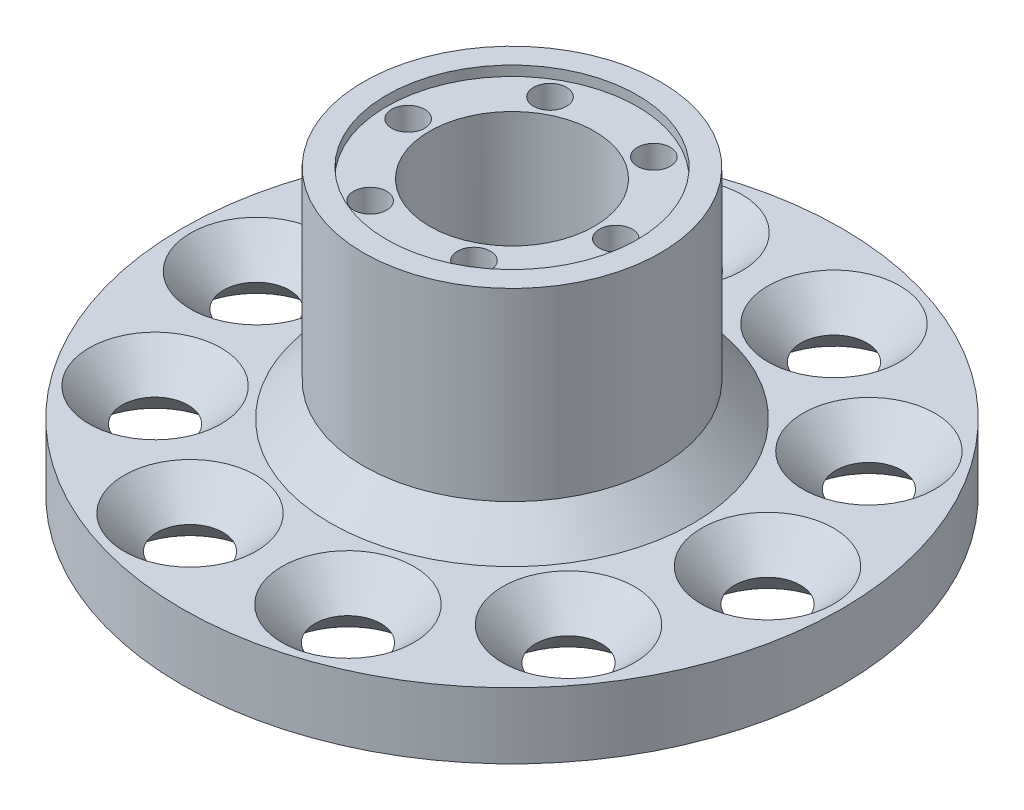
SolidWorks part; units mm, degrees
ref_plane "Front Plane" through (0, 0, 0) normal (0, 0, 1) x (1, 0, 0)
ref_plane "Top Plane" through (0, 0, 0) normal (0, 1, 0) x (1, 0, 0)
ref_plane "Right Plane" through (0, 0, 0) normal (1, 0, 0) x (0, 0, -1)
sketch "Sketch1" plane through (0, 0, 0) normal (0, 1, 0) x (1, 0, 0)
  line L0 (-12.5, 0) -> (-19, 0)
  circle A0 centre (0, 0) radius 19
  circle A1 centre (0, 0) radius 12.5
  circle A2 centre (-15.75, 0) radius 2
  circle A3 centre (-7.875, 13.6399) radius 2
  circle A4 centre (7.875, 13.6399) radius 2
  circle A5 centre (15.75, 0) radius 2
  circle A6 centre (7.875, -13.6399) radius 2
  circle A7 centre (-7.875, -13.6399) radius 2
  point P20 (0, 0)
  dimension "D1" = 6
extrude "Boss-Extrude1" add sketch "Sketch1" along normal blind 15 contours A2 A1 A0 A7 A6 A5 A4 A3 region at (0, 0, -18.4626)
sketch "Sketch2" plane through (0, 15, 0) normal (0, 1, 0) x (1, 0, 0)
  circle A0 centre (0, 0) radius 12.5
  circle A1 centre (0, 0) radius 19
  circle A2 centre (0, 0) radius 22.5
  circle M4 centre (-15.75, 0) radius 2
  circle M5 centre (0, 0) radius 19
  circle M6 centre (-7.875, -13.6399) radius 2
  circle M7 centre (7.875, -13.6399) radius 2
  circle M8 centre (15.75, 0) radius 2
  circle M9 centre (7.875, 13.6399) radius 2
  circle M10 centre (-7.875, 13.6399) radius 2
  circle M11 centre (0, 0) radius 12.5
extrude "Boss-Extrude2" add sketch "Sketch2" along normal blind 5 contours A2 M5 | M5 M7 M9 M11 M10 M8 M6 M4 region at (-18.4626, 15, 0) region at (-21.8636, 15, 0)
sketch "Sketch3" plane through (0, 20, 0) normal (0, 1, 0) x (1, 0, 0)
  circle A0 centre (0, 0) radius 12.5
  circle A1 centre (0, 0) radius 19
extrude "Cut-Extrude1" cut sketch "Sketch3" against normal blind 1.5
sketch "Sketch5" plane through (0, 0, 0) normal (0, -1, 0) x (1, 0, 0)
  circle A0 centre (0, 0) radius 12.5
  circle A1 centre (0, 0) radius 19
  circle A2 centre (15.75, 0) radius 2
  circle A3 centre (7.875, -13.6399) radius 2
  circle A4 centre (-7.875, -13.6399) radius 2
  circle A5 centre (-15.75, 0) radius 2
  circle A6 centre (-7.875, 13.6399) radius 2
  circle A7 centre (7.875, 13.6399) radius 2
  circle A8 centre (0, 0) radius 22.5
  point P19 (0, 0)
  circle M1 centre (-15.75, 0) radius 2
  circle M2 centre (0, 0) radius 19
  circle M3 centre (-7.875, 13.6399) radius 2
  circle M4 centre (7.875, 13.6399) radius 2
  circle M5 centre (15.75, 0) radius 2
  circle M6 centre (7.875, -13.6399) radius 2
  circle M7 centre (-7.875, -13.6399) radius 2
  circle M8 centre (0, 0) radius 12.5
  dimension "D1" = 6
extrude "Boss-Extrude4" add sketch "Sketch5" against normal blind 5 contours A8 M2 | M2 M4 M6 M8 M7 M5 M3 M1 region at (-18.4626, 0, 0) region at (-21.8636, 0, 0)
sketch "Sketch6" plane through (0, 0, 0) normal (0, -1, 0) x (1, 0, 0)
  circle A0 centre (0, 0) radius 12.5
  circle A1 centre (15.75, 0) radius 2
  circle A2 centre (0, 0) radius 22.5
  circle A3 centre (7.875, -13.6399) radius 2
  circle A4 centre (-7.875, -13.6399) radius 2
  circle A5 centre (-15.75, 0) radius 2
  circle A6 centre (-7.875, 13.6399) radius 2
  circle A7 centre (7.875, 13.6399) radius 2
  point P19 (0, 0)
  dimension "D1" = 6
extrude "Boss-Extrude5" add sketch "Sketch6" along normal blind 13
sketch "Sketch7" plane through (0, 15, 0) normal (0, -1, 0) x (1, 0, 0)
  circle A0 centre (0, 0) radius 22.5
  circle A1 centre (0, 0) radius 12.5
  circle A2 centre (15.75, 0) radius 2
  circle A3 centre (7.875, -13.6399) radius 2
  circle A4 centre (-7.875, -13.6399) radius 2
  circle A5 centre (-15.75, 0) radius 2
  circle A6 centre (-7.875, 13.6399) radius 2
  circle A7 centre (7.875, 13.6399) radius 2
  point P19 (0, 0)
  dimension "D1" = 6
extrude "Boss-Extrude6" add sketch "Sketch7" along normal blind 10
sketch "Sketch8" plane through (0, -13, 0) normal (0, -1, 0) x (1, 0, 0)
  circle A0 centre (0, 0) radius 12.5
  circle A1 centre (0, 0) radius 50
  circle A2 centre (15.75, 0) radius 2
  circle A3 centre (7.875, -13.6399) radius 2
  circle A4 centre (-7.875, -13.6399) radius 2
  circle A5 centre (-15.75, 0) radius 2
  circle A6 centre (-7.875, 13.6399) radius 2
  circle A7 centre (7.875, 13.6399) radius 2
  point P19 (0, 0)
  dimension "D1" = 6
extrude "Boss-Extrude7" add sketch "Sketch8" along normal blind 10
chamfer "Chamfer6" distance 15 angle 45 1 edges at (0, -23, -12.5)
sketch "Sketch9" plane through (0, -23, 0) normal (0, -1, 0) x (1, 0, 0)
  circle A0 centre (0, 0) radius 12.5
  circle A3 centre (0, 0) radius 15.75
  circle A4 centre (15.75, 0) radius 2
  circle A5 centre (7.875, -13.6399) radius 2
  circle A6 centre (-7.875, -13.6399) radius 2
  circle A7 centre (-15.75, 0) radius 2
  circle A8 centre (-7.875, 13.6399) radius 2
  circle A9 centre (7.875, 13.6399) radius 2
  circle A10 centre (-15.75, 0) radius 4.25
  circle A11 centre (-7.875, 13.6399) radius 4.25
  circle A12 centre (7.875, 13.6399) radius 4.25
  circle A13 centre (15.75, 0) radius 4.25
  circle A14 centre (7.875, -13.6399) radius 4.25
  circle A15 centre (-7.875, -13.6399) radius 4.25
  point P22 (0, 0)
  point P34 (0, 0)
  dimension "D2" = 6
  dimension "D1" = 6
extrude "Cut-Extrude2" cut sketch "Sketch9" against normal blind 15 contours A3 A7 | A3 A10 A0 A7 | A3 A10 A7 | A3 A7 | A3 A5 | A11 | A12 | A8 | A9 | A13 | A4 | A14 | A5 | A15 | A6 region at (8.2878, -23, -14.3548) region at (-12.5907, -23, 0) region at (-15.5354, -23, 3.1309) region at (-14.8787, -23, 0) region at (-16.5755, -23, 0)
sketch "Sketch10" plane through (0, 18.5, 0) normal (0, 1, 0) x (1, 0, 0)
  circle A0 centre (-15.75, 0) radius 2.5
  circle A1 centre (-7.875, 13.6399) radius 2.5
  circle A2 centre (7.875, 13.6399) radius 2.5
  circle A3 centre (15.75, 0) radius 2.5
  circle A4 centre (7.875, -13.6399) radius 2.5
  circle A5 centre (-7.875, -13.6399) radius 2.5
  point P15 (0, 0)
  dimension "D1" = 6
extrude "Cut-Extrude3" cut sketch "Sketch10" against normal through all both
chamfer "Chamfer7" distance 5 angle 45 1 edges at (0, -13, -22.5)
sketch "Sketch11" plane through (0, -23, 0) normal (0, -1, 0) x (1, 0, 0)
  line L0 (27.5, 0) -> (50, 0)
  circle A0 centre (0, 0) radius 27.5 construction
  circle A1 centre (0, 0) radius 50 construction
  circle A2 centre (38.75, 0) radius 5
  circle A3 centre (31.3494, -22.7767) radius 5
  circle A4 centre (11.9744, -36.8534) radius 5
  circle A5 centre (-11.9744, -36.8534) radius 5
  circle A6 centre (-31.3494, -22.7767) radius 5
  circle A7 centre (-38.75, 0) radius 5
  circle A8 centre (-31.3494, 22.7767) radius 5
  circle A9 centre (-11.9744, 36.8534) radius 5
  circle A10 centre (11.9744, 36.8534) radius 5
  circle A11 centre (31.3494, 22.7767) radius 5
  point P9 (0, 0)
  point P29 (0, 0)
  dimension "D1" = 10
extrude "Cut-Extrude4" cut sketch "Sketch11" against normal through all contours A8 | A9 | A10 | A11 | L0 A2 | L0 A2 | A3 | A4 | A5 | A6 | A7 region at (38.75, -23, 2.1221) region at (38.75, -23, -2.1221) region at (31.3494, -23, -22.7767) region at (11.9744, -23, -36.8534) region at (-11.9744, -23, -36.8534) region at (-31.3494, -23, -22.7767) region at (-38.75, -23, 0) region at (-31.3494, -23, 22.7767) region at (-11.9744, -23, 36.8534) region at (11.9744, -23, 36.8534) region at (31.3494, -23, 22.7767)
chamfer "Chamfer8" distance 5 angle 45 20 edges at (-31.3494, -13, -27.7767) (-11.9744, -13, -41.8534) (11.9744, -13, -41.8534) (31.3494, -13, -27.7767) (38.75, -13, -5) (31.3494, -13, 17.7767) (11.9744, -13, 31.8534) (-11.9744, -13, 31.8534) (-31.3494, -13, 17.7767) (-38.75, -13, -5) (-38.75, -23, -5) (-31.3494, -23, -27.7767) (-11.9744, -23, -41.8534) (11.9744, -23, -41.8534) (31.3494, -23, -27.7767) (38.75, -23, -5) (31.3494, -23, 17.7767) (11.9744, -23, 31.8534) (-11.9744, -23, 31.8534) (-31.3494, -23, 17.7767)
